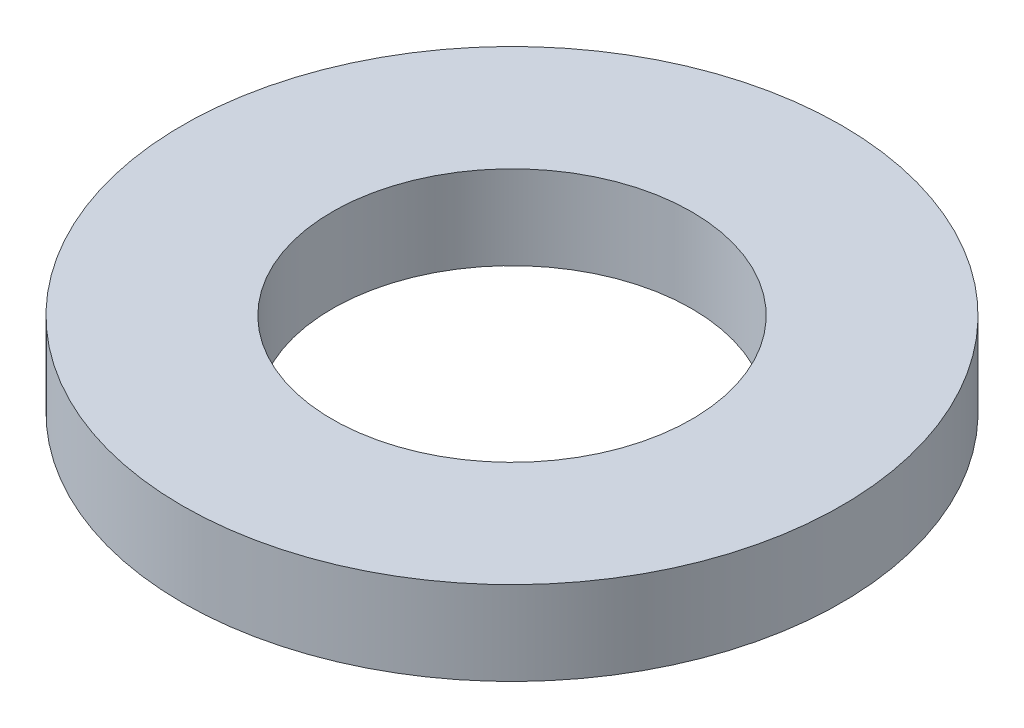
SolidWorks part; units mm, degrees
ref_plane "Front Plane" through (0, 0, 0) normal (0, 0, 1) x (1, 0, 0)
ref_plane "Top Plane" through (0, 0, 0) normal (0, 1, 0) x (1, 0, 0)
ref_plane "Right Plane" through (0, 0, 0) normal (1, 0, 0) x (0, 0, -1)
sketch "Sketch1" plane through (0, 0, 0) normal (0, 1, 0) x (1, 0, 0)
  circle A0 centre (0, 0) radius 82.5
  dimension "FLANGE_OD" = 165
extrude "Boss-Extrude1" add sketch "Sketch1" along normal blind 21
sketch "Sketch2" plane through (0, 0, 0) normal (0, 1, 0) x (1, 0, 0)
  circle A0 centre (0, 0) radius 45
  dimension "BORE_D" = 90
extrude "Cut-Extrude1" cut sketch "Sketch2" along normal through all
sketch "Sketch3" plane through (0, 21, 0) normal (0, 1, 0) x (1, 0, 0)
  circle A0 centre (0, 0) radius 26.7666 construction
  circle A1 centre (-26.7666, 0) radius 4.948
  dimension "BOLT_D" = 9.8961
  dimension "BOLT_PCD" = 53.5332
extrude "Cut-Extrude2" cut sketch "Sketch3" against normal blind 15.8754 rebuild error yes
pattern_circular "CirPattern1" count 3 over 360 rebuild error yes
